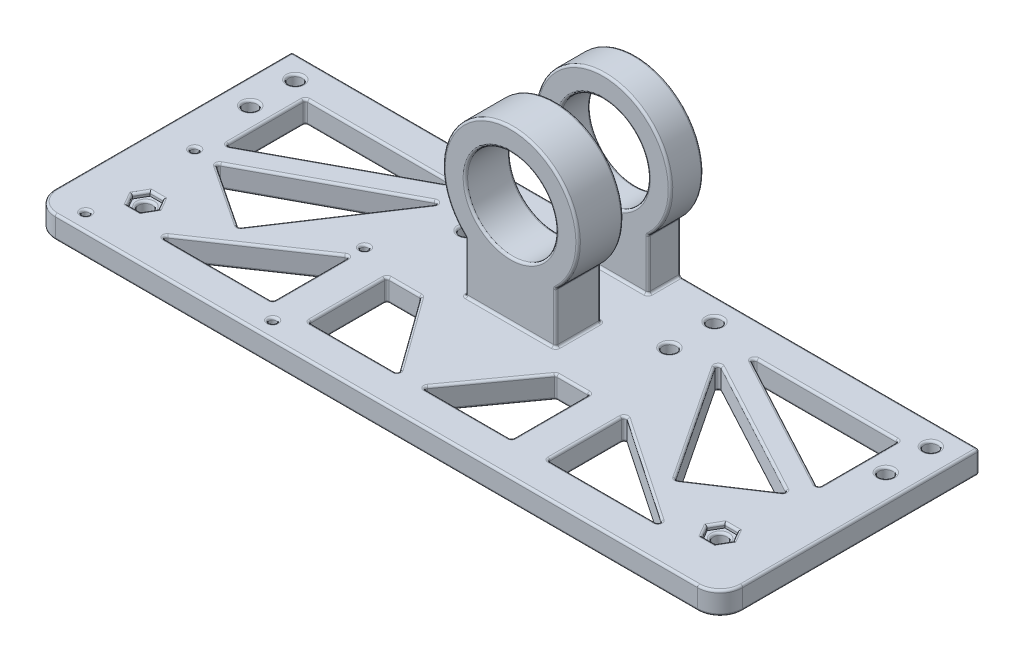
SolidWorks part; units mm, degrees
ref_plane "Front Plane" through (0, 0, 0) normal (0, 0, 1) x (1, 0, 0)
ref_plane "Top Plane" through (0, 0, 0) normal (0, 1, 0) x (1, 0, 0)
ref_plane "Right Plane" through (0, 0, 0) normal (1, 0, 0) x (0, 0, -1)
sketch "Sketch1" plane through (0, 0, 0) normal (0, 1, 0) x (1, 0, 0)
  line L0 (152.5, 115) -> (152.5, 0) construction
  line L1 (0, 0) -> (305, 0)
  line L2 (0, 0) -> (0, 115)
  line L3 (0, 115) -> (305, 115)
  line L4 (305, 0) -> (305, 115)
  line L5 (25, 90) -> (280, 90) construction
  line L6 (280, 25) -> (280, 90) construction
  line L7 (25, 25) -> (280, 25) construction
  line L8 (25, 25) -> (25, 90) construction
  line L9 (152.5, 57.5) -> (25, 57.5) construction
  line L10 (30.7735, 90) -> (27.8868, 95) construction
  line L11 (27.8868, 95) -> (22.1132, 95) construction
  line L12 (22.1132, 95) -> (19.2265, 90) construction
  line L13 (19.2265, 90) -> (22.1132, 85) construction
  line L14 (22.1132, 85) -> (27.8868, 85) construction
  line L15 (27.8868, 85) -> (30.7735, 90) construction
  line L16 (27.8868, 30) -> (30.7735, 25) construction
  line L17 (22.1132, 30) -> (27.8868, 30) construction
  line L18 (19.2265, 25) -> (22.1132, 30) construction
  line L19 (22.1132, 20) -> (19.2265, 25) construction
  line L20 (27.8868, 20) -> (22.1132, 20) construction
  line L21 (30.7735, 25) -> (27.8868, 20) construction
  line L22 (282.8868, 30) -> (277.1132, 30) construction
  line L23 (285.7735, 25) -> (282.8868, 30) construction
  line L24 (282.8868, 20) -> (285.7735, 25) construction
  line L25 (277.1132, 20) -> (282.8868, 20) construction
  line L26 (274.2265, 25) -> (277.1132, 20) construction
  line L27 (277.1132, 30) -> (274.2265, 25) construction
  line L28 (277.1132, 85) -> (274.2265, 90) construction
  line L29 (282.8868, 85) -> (277.1132, 85) construction
  line L30 (285.7735, 90) -> (282.8868, 85) construction
  line L31 (282.8868, 95) -> (285.7735, 90) construction
  line L32 (277.1132, 95) -> (282.8868, 95) construction
  line L33 (274.2265, 90) -> (277.1132, 95) construction
  line L34 (107.5, 105) -> (107.5, 115) construction
  line L35 (132.5, 0) -> (172.5, 0) construction
  line L37 (132.5, 115) -> (172.5, 115) construction
  line L41 (132.5, 25) -> (172.5, 25) construction
  line L50 (305, 14.5) -> (253.3, 14.5) construction
  line L51 (30.7735, 90) -> (22.1132, 95) construction
  line L54 (0, 115) -> (90.0836, 115) construction
  line L55 (0, 115) -> (0, 84.5) construction
  line L62 (0, 84.5) -> (0, 69.5) construction
  line L64 (62, 0) -> (62, 115) construction
  line L65 (253.3, 14.5) -> (253.3, 0) construction
  line L67 (253.3, 14.5) -> (280.2, 14.5) construction
  circle A1 centre (25, 90) radius 5 construction
  circle A3 centre (280, 25) radius 3
  circle A4 centre (25, 25) radius 3
  circle A18 centre (107.5, 105) radius 3
  circle A20 centre (107.5, 85) radius 3
  circle A23 centre (197.5, 105) radius 3
  circle A24 centre (197.5, 85) radius 3
  circle A27 centre (107.5, 65) radius 3 [skipped]
  circle A28 centre (107.5, 45) radius 3 [skipped]
  circle A29 centre (11.5, 85) radius 3
  circle A30 centre (11.5, 105) radius 3
  circle A31 centre (293.5, 105) radius 3
  circle A32 centre (293.5, 85) radius 3
  dimension "D3" = 6
  dimension "D1" = 305
  dimension "D2" = 115
  dimension "D5" = 10
  dimension "D6" = 40
  dimension "D15" = 62
  dimension "D18" = 51.7
  dimension "D19" = 14.5
  dimension "D20" = 26.9
  dimension "D8" = 20
  dimension "D9" = 45
  dimension "D11" = 11.5
  dimension "D4" = 25
  dimension "D14" = 2
  dimension "D7" = 4
  dimension "D10" = 2
extrude "Boss-Extrude1" add sketch "Sketch1" along normal blind 10
sketch "Sketch7" plane through (0, 10, 0) normal (0, 1, 0) x (1, 0, 0)
  line L0 (0, 0) -> (305, 0) construction
  line L1 (132.5, 59.5) -> (172.5, 59.5)
  line L2 (132.5, 59.5) -> (132.5, 79.5)
  line L3 (132.5, 79.5) -> (172.5, 79.5)
  line L4 (172.5, 59.5) -> (172.5, 79.5)
  line L5 (152.5, 0) -> (152.5, 115) construction
  line L6 (305, 115) -> (0, 115) construction
  line L18 (132.5, 100.5) -> (172.5, 100.5)
  line L19 (132.5, 100.5) -> (132.5, 115)
  line L20 (132.5, 115) -> (172.5, 115)
  line L21 (172.5, 100.5) -> (172.5, 115)
  point P11 (152.5, 79.5)
  point P20 (152.5, 100.5)
  dimension "D1" = 40
  dimension "D2" = 20
  dimension "D4" = 14.5
  dimension "D3" = 21
extrude "Boss-Extrude2" add sketch "Sketch7" along normal blind 22.6393
sketch "Sketch11" plane through (0, 0, -59.5) normal (0, 0, 1) x (1, 0, 0)
  circle A0 centre (152.5, 55) radius 30
  circle A1 centre (152.5, 55) radius 20.05
  dimension "D1" = 60
  dimension "D2" = 40.1
extrude "Boss-Extrude3" add sketch "Sketch11" against normal up to surface (55.5 mm away) up to face at (152.5, 13.1598, -115)
ref_plane "Plane1" through (0, 0, -57.5) normal (0, 0, 1) x (1, 0, 0)
sketch "Sketch12" plane through (305, 0, 0) normal (1, 0, 0) x (0, 0, -1)
  line L0 (115, 85) -> (59.5, 85) construction
  line L1 (79.5, 10) -> (100.5, 10)
  line L2 (79.5, 10) -> (79.5, 85)
  line L3 (79.5, 85) -> (100.5, 85)
  line L4 (100.5, 10) -> (100.5, 85)
  line L6 (100.5, 32.6393) -> (100.5, 10) construction
extrude "Cut-Extrude2" cut sketch "Sketch12" against normal through all
sketch "Sketch6" plane through (0, 10, 0) normal (0, 1, 0) x (1, 0, 0)
  line L0 (152.5, 115) -> (152.5, 0) construction
  line L8 (0, 0) -> (305, 0) construction
  line L9 (152.5, 57.5) -> (0, 57.5) construction
  line L10 (0, 115) -> (0, 0) construction
  line L29 (27.8868, 30) -> (30.7735, 25)
  line L30 (274.2265, 25) -> (277.1132, 20)
  line L31 (277.1132, 20) -> (282.8868, 20)
  line L32 (282.8868, 20) -> (285.7735, 25)
  line L33 (285.7735, 25) -> (282.8868, 30)
  line L34 (282.8868, 30) -> (277.1132, 30)
  line L35 (277.1132, 30) -> (274.2265, 25)
  line L36 (22.1132, 30) -> (27.8868, 30)
  line L37 (19.2265, 25) -> (22.1132, 30)
  line L38 (22.1132, 20) -> (19.2265, 25)
  line L39 (27.8868, 20) -> (22.1132, 20)
  line L40 (30.7735, 25) -> (27.8868, 20)
  circle A0 centre (280, 25) radius 5 construction
  dimension "D1" = 10
extrude "Cut-Extrude1" cut sketch "Sketch6" against normal blind 2
sketch "Sketch16" plane through (0, 10, 0) normal (0, 1, 0) x (1, 0, 0)
  line L0 (0, 0) -> (305, 0) construction
  line L1 (0, 115) -> (0, 0) construction
  line L2 (21, 100) -> (87.6199, 100)
  line L3 (16, 55.866) -> (107.5, 55.866) construction
  line L4 (16, 55.866) -> (16, 105) construction
  line L5 (16, 105) -> (107.5, 105) construction
  line L6 (107.5, 55.866) -> (107.5, 105) construction
  line L7 (16, 55.866) -> (107.5, 105) construction
  line L8 (16, 105) -> (107.5, 55.866) construction
  line L9 (21, 64.2262) -> (87.6199, 100)
  line L10 (21, 64.2262) -> (21, 100)
  line L11 (25.7309, 55.4161) -> (55.5519, 35.6556)
  line L12 (25.7309, 55.4161) -> (92.3508, 91.1899)
  line L13 (55.5519, 35.6556) -> (92.3508, 91.1899)
  line L14 (152.5, 115) -> (152.5, 0) construction
  line L15 (182.5, 115) -> (122.5, 115) construction
  line L16 (40.4012, 15) -> (91.45, 49.6549)
  line L17 (16, 63.8113) -> (98.95, 63.8113) construction
  line L18 (16, 63.8113) -> (16, 7.5) construction
  line L19 (16, 7.5) -> (98.95, 7.5) construction
  line L20 (98.95, 63.8113) -> (98.95, 7.5) construction
  line L21 (16, 63.8113) -> (98.95, 7.5) construction
  line L22 (16, 7.5) -> (98.95, 63.8113) construction
  line L23 (91.45, 49.6549) -> (91.45, 15)
  line L24 (40.4012, 15) -> (91.45, 15)
  line L25 (107.5, 49.6549) -> (107.5, 15)
  line L26 (107.5, 15) -> (147.5, 15)
  line L27 (147.5, 15) -> (122.5, 49.6549)
  line L28 (122.5, 49.6549) -> (107.5, 49.6549)
  line L29 (122.5, 79.5) -> (122.5, 59.5) construction
  line L30 (284, 64.2262) -> (284, 100)
  line L31 (284, 64.2262) -> (217.3801, 100)
  line L32 (284, 100) -> (217.3801, 100)
  line L33 (279.2691, 55.4161) -> (212.6492, 91.1899)
  line L34 (249.4481, 35.6556) -> (212.6492, 91.1899)
  line L35 (279.2691, 55.4161) -> (249.4481, 35.6556)
  line L36 (264.5988, 15) -> (213.55, 15)
  line L37 (213.55, 49.6549) -> (213.55, 15)
  line L38 (264.5988, 15) -> (213.55, 49.6549)
  line L39 (157.5, 15) -> (182.5, 49.6549)
  line L40 (197.5, 15) -> (157.5, 15)
  line L41 (197.5, 49.6549) -> (197.5, 15)
  line L42 (182.5, 49.6549) -> (197.5, 49.6549)
  circle A0 centre (16, 7.5) radius 1.55
  circle A1 centre (98.95, 7.5) radius 1.55
  circle A2 centre (16, 55.866) radius 1.55
  circle A3 centre (91.33, 55.866) radius 1.55
  point P10 (61.75, 80.433)
  point P18 (57.475, 35.6556)
  dimension "D1" = 3.1
  dimension "D2" = 7.5
  dimension "D3" = 82.95
  dimension "D4" = 16
  dimension "D5" = 48.366
  dimension "D6" = 75.33
  dimension "D7" = 5
  dimension "D8" = 7.5
  dimension "D9" = 5
extrude "Cut-Extrude3" cut sketch "Sketch16" against normal through all
fillet "Fillet3" radius 10 2 edges at (305, 5, 0) (0, 5, 0)
chamfer "Chamfer2" distance 1.65 4 edges at (98.95, 0, -5.95) (91.33, 0, -54.316) (16, 0, -5.95) (16, 0, -54.316)
fillet "Fillet5" radius 1 156 edges at (54.31, 0, -82.1131) (73.9513, 0, -63.4227) (91.45, 0, -32.3275) (135, 0, -32.3275) (197.5, 0, -32.3275) (239.0744, 0, -15) (284, 0, -82.1131) (264.3586, 0, -45.5358) (0, 0, -62.5) (2.9289, 0, -2.9289) (152.5, 0, 0) (302.0711, 0, -2.9289) (293.5, 0, -108) (293.5, 0, -88) (197.5, 0, -108) (197.5, 0, -88) (280, 8, -22) (280, 0, -22) (107.5, 0, -102) (107.5, 0, -82) (25, 0, -28) (25, 8, -28) (11.5, 0, -102) (11.5, 0, -82) (21, 0, -82.1131) (21, 5, -64.2262) (40.6414, 0, -45.5358) (55.5519, 5, -35.6556) (65.9256, 0, -15) (91.45, 5, -15) (87.6199, 5, -100) (54.31, 0, -100) (21, 5, -100) (92.3508, 5, -91.1899) (59.0409, 0, -73.303) (25.7309, 5, -55.4161) (91.45, 5, -49.6549) (65.9256, 0, -32.3275) (40.4012, 5, -15) (107.5, 0, -32.3275) (122.5, 5, -49.6549) (115, 0, -49.6549) (107.5, 5, -49.6549) (107.5, 5, -15) (127.5, 0, -15) (147.5, 5, -15) (177.5, 0, -15) (197.5, 5, -15) (197.5, 5, -49.6549) (190, 0, -49.6549) (182.5, 5, -49.6549) (170, 0, -32.3275) (157.5, 5, -15) (264.5988, 5, -15) (239.0744, 0, -32.3275) (213.55, 5, -49.6549) (213.55, 0, -32.3275) (213.55, 5, -15) (284, 5, -100) (250.69, 0, -100) (217.3801, 5, -100) (250.69, 0, -82.1131) (284, 5, -64.2262) (279.2691, 5, -55.4161) (245.9591, 0, -73.303) (212.6492, 5, -91.1899) (231.0487, 0, -63.4227) (249.4481, 5, -35.6556) (305, 0, -62.5) (132.45, 55, -100.5) (132.5, 21.3197, -100.5) (172.5, 21.3197, -100.5) (172.55, 55, -115) (0, 5, -115) (152.5, 0, -115) (305, 5, -115) (172.5, 21.3197, -115) (132.5, 21.3197, -115) (132.5, 32.6393, -107.75) (152.5, 85, -115) (172.5, 32.6393, -107.75) (152.5, 85, -100.5) (172.55, 55, -79.5) (172.5, 21.3197, -79.5) (152.5, 85, -79.5) (172.5, 32.6393, -69.5) (132.5, 21.3197, -79.5) (132.5, 32.6393, -69.5) (172.55, 55, -59.5) (132.5, 21.3197, -59.5) (152.5, 85, -59.5) (172.5, 21.3197, -59.5) (107.5, 10, -102) (11.5, 10, -102) (107.5, 10, -82) (197.5, 10, -88) (11.5, 10, -82) (293.5, 10, -88) (2.9289, 10, -2.9289) (0, 10, -62.5) (66.25, 10, -115) (132.5, 10, -107.75) (152.5, 10, -100.5) (172.5, 10, -107.75) (238.75, 10, -115) (305, 10, -62.5) (302.0711, 10, -2.9289) (152.5, 10, 0) (293.5, 10, -108) (197.5, 10, -108) (132.5, 10, -69.5) (152.5, 10, -59.5) (172.5, 10, -69.5) (152.5, 10, -79.5) (280, 10, -20) (284.3301, 10, -22.5) (284.3301, 10, -27.5) (280, 10, -30) (275.6699, 10, -27.5) (275.6699, 10, -22.5) (20.6699, 10, -22.5) (25, 10, -20) (29.3301, 10, -22.5) (29.3301, 10, -27.5) (25, 10, -30) (20.6699, 10, -27.5) (127.5, 10, -15) (135, 10, -32.3275) (115, 10, -49.6549) (107.5, 10, -32.3275) (231.0487, 10, -63.4227) (264.3586, 10, -45.5358) (245.9591, 10, -73.303) (190, 10, -49.6549) (170, 10, -32.3275) (177.5, 10, -15) (197.5, 10, -32.3275) (239.0744, 10, -15) (239.0744, 10, -32.3275) (213.55, 10, -32.3275) (16, 10, -5.95) (98.95, 10, -5.95) (54.31, 10, -100) (21, 10, -82.1131) (54.31, 10, -82.1131) (16, 10, -54.316) (284, 10, -82.1131) (250.69, 10, -100) (250.69, 10, -82.1131) (65.9256, 10, -32.3275) (65.9256, 10, -15) (91.45, 10, -32.3275) (91.33, 10, -54.316) (40.6414, 10, -45.5358) (73.9513, 10, -63.4227) (59.0409, 10, -73.303)
equation "\"joint_width\"=4"
equation "\"short_base_length\"=11.5"
equation "\"D2@Sketch1\"=\"short_base_length\""
equation "\"outer_diam_main_joint\"=6"
equation "\"D1@Sketch11\"=\"outer_diam_main_joint\""
equation "\"D1@Sketch7\"=\"outer_diam_main_joint\"-2"
equation "\"D1@Boss-Extrude2\"=(\"outer_diam_main_joint\"/2)+1.5cm-sqr((\"outer_diam_main_joint\"/2)^2-((\"outer_diam_main_joint\"-2)/2)^2)"
equation "\"D6@Sketch1\"=\"outer_diam_main_joint\"-2"
equation "\"pulleyside\"=1.5"
